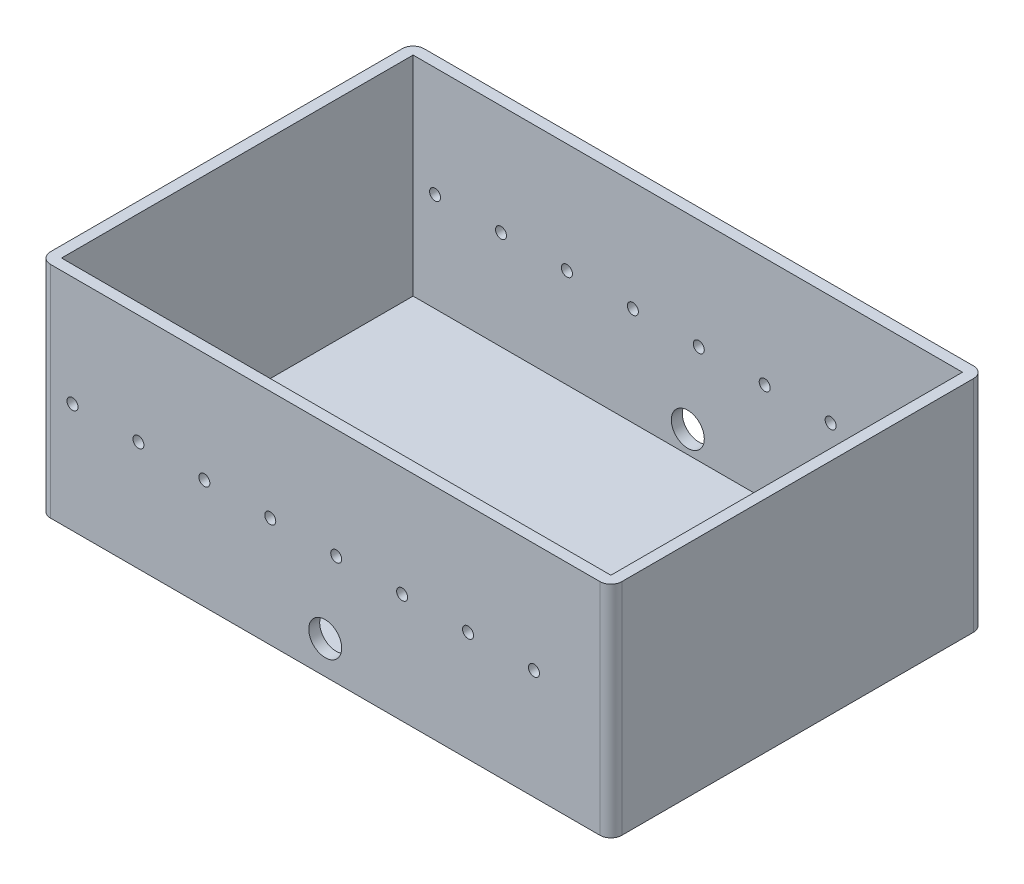
SolidWorks part; units mm, degrees
material "ABS"
ref_plane "Front Plane" through (0, 0, 0) normal (0, 0, 1) x (1, 0, 0)
ref_plane "Top Plane" through (0, 0, 0) normal (0, 1, 0) x (1, 0, 0)
ref_plane "Right Plane" through (0, 0, 0) normal (1, 0, 0) x (0, 0, -1)
sketch "Sketch1" plane through (0, 0, 0) normal (1, 0, 0) x (0, 0, -1)
  line L0 (0, 0) -> (-170, 0)
  line L1 (-170, 0) -> (-170, 100)
  line L2 (-170, 100) -> (-165, 100)
  line L3 (-165, 100) -> (-165, 5)
  line L4 (-165, 5) -> (-5, 5)
  line L5 (-5, 5) -> (-5, 100)
  line L6 (-5, 100) -> (0, 100)
  line L7 (0, 100) -> (0, 0)
  line L8 (-5, 100) -> (-165, 100)
  dimension "D1" = 100
  dimension "D2" = 5
  dimension "D3" = 5
  dimension "D4" = 170
extrude "Boss-Extrude1" add sketch "Sketch1" along normal mid plane 260 contours L7 L6 L5 L4 L3 L2 L1 L0 | L5 L8 L3 L4 region at (0, 1.9723, 85) region at (0, 52.5, 85)
extrude "Cut-Extrude1" cut sketch "Sketch1<3>" against normal mid plane 250 contours L5 L8 L3 L4 region at (0, 52.5, 85)
sketch "Sketch1<3>" plane through (0, 0, 0) normal (1, 0, 0) x (0, 0, -1) same geometry as "Sketch1"
fillet "Fillet1" radius 5 4 edges at (-130, 50, 0) (130, 50, 0) (-130, 50, 170) (130, 50, 170)
sketch "Sketch2" plane through (0, 0, 170) normal (0, 0, 1) x (1, 0, 0)
  line L0 (125, 0) -> (-125, 0) construction
  line L1 (125, 0) -> (125, 100) construction
  circle A0 centre (95, 50) radius 2.5
  circle A1 centre (65, 50) radius 2.5
  circle A2 centre (35, 50) radius 2.5
  circle A3 centre (5, 50) radius 2.5
  circle A4 centre (-25, 50) radius 2.5
  circle A5 centre (-55, 50) radius 2.5
  circle A6 centre (-85, 50) radius 2.5
  circle A7 centre (-115, 50) radius 2.5
  dimension "D1" = 5
  dimension "D2" = 50
  dimension "D3" = 30
  dimension "D5" = 30
  dimension "D4" = 8
extrude "Cut-Extrude2" cut sketch "Sketch2" against normal through all
sketch "Sketch3" plane through (0, 0, 170) normal (0, 0, 1) x (1, 0, 0)
  line L0 (125, 0) -> (-125, 0) construction
  circle A0 centre (0, 15) radius 7.5
  dimension "D1" = 15
  dimension "D2" = 15
extrude "Cut-Extrude3" cut sketch "Sketch3" against normal through all
sketch "Sketch4" plane through (0, 0, 170) normal (0, 0, 1) x (1, 0, 0)
  line L0 (-60, 100) -> (-60, 80)
  line L1 (125, 100) -> (-125, 100) construction
  line L2 (-30, 50) -> (130, 50)
  line L3 (130, 100) -> (130, 0) construction
  line L4 (-130, 0) -> (-130, 100) construction
  line L5 (125, 0) -> (-125, 0) construction
  line L6 (-60, 100) -> (130, 100)
  line L7 (130, 100) -> (130, 50)
  arc A0 (-60, 80) -> (-30, 50) centre (-30, 80) ccw
  dimension "D3" = 30
  dimension "D1" = 70
  dimension "D2" = 50
